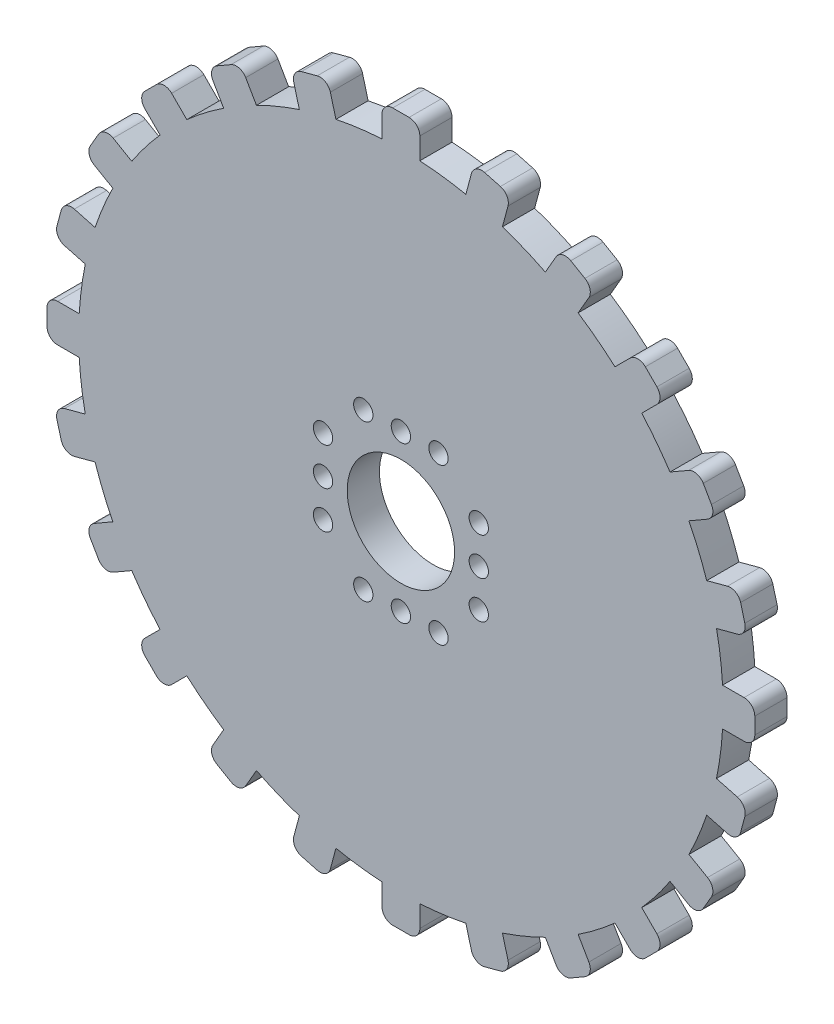
SolidWorks part; units mm, degrees
ref_plane "Front Plane" through (0, 0, 0) normal (0, 0, 1) x (1, 0, 0)
ref_plane "Top Plane" through (0, 0, 0) normal (0, 1, 0) x (1, 0, 0)
ref_plane "Right Plane" through (0, 0, 0) normal (1, 0, 0) x (0, 0, -1)
sketch "Sketch1" plane through (0, 0, 0) normal (0, 0, 1) x (1, 0, 0)
  circle A0 centre (0, 0) radius 30
  circle A1 centre (0, 0) radius 5
  circle A2 centre (-3.5, 7.25) radius 0.7
  circle A3 centre (0, 7.25) radius 0.7
  circle A4 centre (3.5, 7.25) radius 0.7
  circle A5 centre (7.25, 3.5) radius 0.7
  circle A6 centre (7.25, 0) radius 0.7
  circle A7 centre (7.25, -3.5) radius 0.7
  circle A8 centre (3.5, -7.25) radius 0.7
  circle A9 centre (0, -7.25) radius 0.7
  circle A10 centre (-3.5, -7.25) radius 0.7
  circle A11 centre (-7.25, -3.5) radius 0.7
  circle A12 centre (-7.25, 0) radius 0.7
  circle A13 centre (-7.25, 3.5) radius 0.7
  point P33 (0, 0)
  dimension "D1" = 60
  dimension "D2" = 10
  dimension "D4" = 1.4
  dimension "D3" = 4
extrude "Boss-Extrude1" add sketch "Sketch1" along normal blind 3
sketch "Sketch2" plane through (0, 0, 3) normal (0, 0, 1) x (1, 0, 0)
  line L0 (30, 0) -> (-30, 0) construction
  line L1 (0, 30) -> (0, -30) construction
  line L3 (29.9482, 1.7626) -> (31.9482, 1.7626)
  line L4 (29.9482, 1.7626) -> (29.9482, -1.7626)
  line L5 (29.9482, -1.7626) -> (31.9482, -1.7626)
  line L6 (32.9482, 0.7626) -> (32.9482, -0.7626)
  circle A0 centre (0, 0) radius 30 construction
  arc A1 (32.9482, -0.7626) -> (31.9482, -1.7626) centre (31.9482, -0.7626) cw
  arc A2 (31.9482, 1.7626) -> (32.9482, 0.7626) centre (31.9482, 0.7626) cw
  point P12 (29.9482, 0)
  point P17 (32.9482, 1.7626)
  dimension "D2" = 1
  dimension "D1" = 3
extrude "Boss-Extrude2" add sketch "Sketch2" against normal blind 3
ref_axis "Axis1" through (0, 0, -0.15) along (0, 0, 1)
pattern_circular "CirPattern2" count 24 over 360 about axis through (0, 0, -0.15) along (0, 0, 1) of "Boss-Extrude2"
hole_wizard "Ø1.8 (1.8) Diameter Hole1" positions "Sketch4" profile "Sketch3" hole size "Ø1.8" standard "ANSI Metric"
sketch "Sketch4" plane through (0, 0, 3) normal (0, 0, 1) x (1, 0, 0)
  point P0 (-7.25, 0)
  point P6 (7.25, 0)
  point P9 (0, -7.25)
  point P12 (0, 7.25)
  point P15 (-3.5, 7.25)
  point P18 (3.5, 7.25)
  point P21 (7.25, 3.5)
  point P24 (7.25, -3.5)
  point P28 (-3.5, -7.25)
  point P31 (3.5, -7.25)
  point P34 (-7.25, -3.5)
  point P37 (-7.25, 3.5)
sketch "Sketch3" plane through (-7.25, 0, 3) normal (1, 0, 0) x (0, -1, 0)
  line L0 (0, 0) -> (0, 10.5408)
  line L1 (0, 10.5408) -> (0.9, 10)
  line L2 (0.9, 10) -> (0.9, 0)
  line L5 (0.9, 0) -> (0, 0)
  line L10 (0, 10.5408) -> (-0.9, 10) construction
  line L11 (0, -6.35) -> (0, 107.95) construction
  dimension "Hole Dia." = 1.8
  dimension "Hole Depth" = 10
  dimension "Drill Angle" = 118
